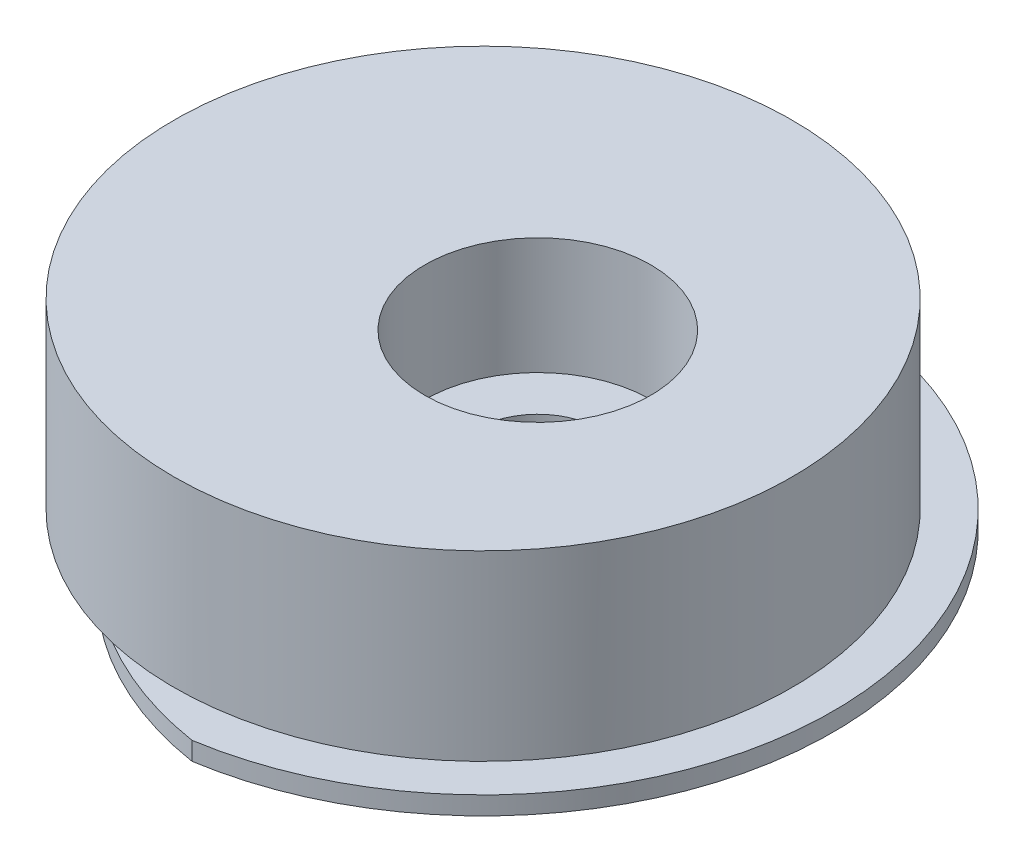
SolidWorks part; units mm, degrees
ref_plane "Front Plane" through (0, 0, 0) normal (0, 0, 1) x (1, 0, 0)
ref_plane "Top Plane" through (0, 0, 0) normal (0, 1, 0) x (1, 0, 0)
ref_plane "Right Plane" through (0, 0, 0) normal (1, 0, 0) x (0, 0, -1)
sketch "Sketch1" plane through (0, 0, 0) normal (0, 1, 0) x (1, 0, 0)
  line L0 (-1.815, 0) -> (1.815, 0) construction
  line L1 (0, -8.03) -> (0, 8.03) construction
  circle A0 centre (1.5, 0) radius 9.6
  circle A1 centre (-1.5, 0) radius 9.6
  dimension "D1" = 19.2
  dimension "D2" = 1.5
extrude "Boss-Extrude1" add sketch "Sketch1" along normal blind 0.5 contours A1 A0 region at (0, 0, 0)
sketch "Sketch2" plane through (0, 0.5, 0) normal (0, 1, 0) x (1, 0, 0)
  line L0 (-0.275, 0) -> (0.275, 0) construction
  line L1 (0, -0.275) -> (0, 0.275) construction
  circle A0 centre (-1.5, 0) radius 8.475
  point P4 (-1.6656, 0)
  dimension "D2" = 1.5
  dimension "D1" = 16.95
extrude "Boss-Extrude2" add sketch "Sketch2" along normal blind 5
sketch "Sketch3" plane through (0, 0, 0) normal (0, 1, 0) x (1, 0, 0)
  line L0 (0, -3.025) -> (0, 3.025) construction
  circle A0 centre (0, 5.8) radius 1.65
  circle A1 centre (0, -5.8) radius 1.35
  dimension "D1" = 3.3
  dimension "D3" = 2.7
  dimension "D2" = 5.8
  dimension "D4" = 5.8
extrude "Cut-Extrude1" cut sketch "Sketch3" along normal blind 4
sketch "Sketch4" plane through (0, 5.5, 0) normal (0, 1, 0) x (1, 0, 0)
  circle A0 centre (0, 0) radius 1.7
  dimension "D1" = 3.4
extrude "Cut-Extrude2" cut sketch "Sketch4" against normal through all
sketch "Sketch5" plane through (0, 5.5, 0) normal (0, 1, 0) x (1, 0, 0)
  circle A0 centre (0, 0) radius 3.1
  dimension "D1" = 6.2
extrude "Cut-Extrude3" cut sketch "Sketch5" against normal blind 3.2
equation "\"pin_circle_R\" = 27"
equation "\"ecc\" = 1.5"
equation "\"n_pins\" = 11"
equation "\"pin_d\" = 3"
equation "\"out_pin_R\" = 18.5"
equation "\"disc_clr\" = 0.1"
equation "\"seat_6803\" = 26.1"
equation "\"disc_t\" = 5"
equation "\"out_hole_clr\" = 0.2"
equation "\"boss_17\" = 16.95"
equation "\"rotor_bolt_R\" = 10"
equation "\"m25_clr\" = 2.8"
equation "\"m25_head\" = 5"
equation "\"insert_hole\" = 4.6"
equation "\"csk\" = 0.6"
equation "\"peg_d\" = 3.0"
equation "\"plug_d\" = 8.4"
equation "\"peg_clr\" = 0.3"
equation "\"m3_clr\" = 3.4"
equation "\"m3_head\" = 6.2"
equation "\"D2@Sketch1\"=\"ecc\""
equation "\"D1@Sketch2\"=\"boss_17\""
equation "\"D1@Sketch3\"=\"peg_d\"+\"peg_clr\""
equation "\"D3@Sketch3\"=\"peg_d\"-0.6+\"peg_clr\""
equation "\"D2@Sketch2\"=\"ecc\""
equation "\"D1@Sketch4\"=\"m3_clr\""
equation "\"D1@Sketch5\"=\"m3_head\""
